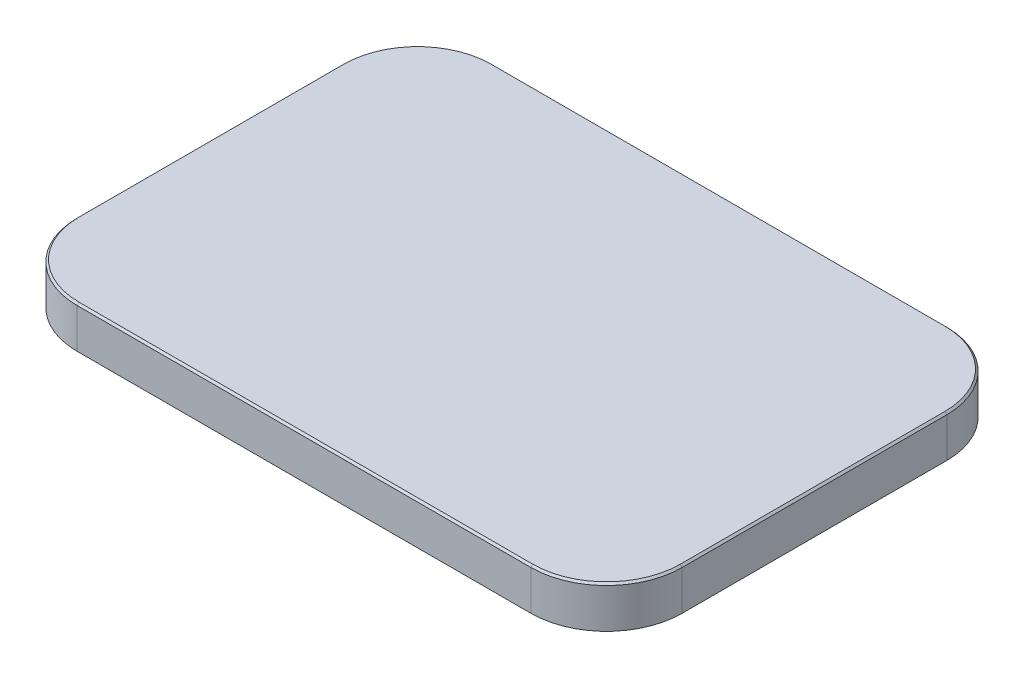
SolidWorks part; units mm, degrees
ref_plane "Front Plane" through (0, 0, 0) normal (0, 0, 1) x (1, 0, 0)
ref_plane "Top Plane" through (0, 0, 0) normal (0, 1, 0) x (1, 0, 0)
ref_plane "Right Plane" through (0, 0, 0) normal (1, 0, 0) x (0, 0, -1)
sketch "Sketch1" plane through (0, 0, 0) normal (0, 1, 0) x (1, 0, 0)
  line L1 (-80, -55) -> (80, -55)
  line L2 (-80, -55) -> (-80, 55)
  line L3 (-80, 55) -> (80, 55)
  line L4 (80, -55) -> (80, 55)
  line L5 (-80, -55) -> (80, 55) construction
  line L6 (-80, 55) -> (80, -55) construction
  point P0 (0, 0)
  dimension "D1" = 110
  dimension "D2" = 160
extrude "Boss-Extrude1" add sketch "Sketch1" against normal blind 1 contours L2 L1 L4 L3
fillet "Fillet1" radius 20 4 edges at (80, -0.5, -55) (80, -0.5, 55) (-80, -0.5, 55) (-80, -0.5, -55)
sketch "Sketch2" plane through (0, -1, 0) normal (0, -1, 0) x (1, 0, 0)
  line L0 (-79, 35) -> (-79, -35)
  line L1 (-60, -54) -> (60, -54)
  line L2 (79, -35) -> (79, 35)
  line L3 (60, 54) -> (-60, 54)
  line L4 (-60, -55) -> (60, -55)
  line L5 (80, -35) -> (80, 35)
  line L6 (60, 55) -> (-60, 55)
  line L7 (-80, 35) -> (-80, -35)
  line L8 (-60, -55) -> (60, -55)
  line L9 (80, -35) -> (80, 35)
  line L10 (60, 55) -> (-60, 55)
  line L11 (-80, 35) -> (-80, -35)
  arc A0 (-60, 54) -> (-79, 35) centre (-60, 35) ccw
  arc A1 (-79, -35) -> (-60, -54) centre (-60, -35) ccw
  arc A2 (60, -54) -> (79, -35) centre (60, -35) ccw
  arc A3 (79, 35) -> (60, 54) centre (60, 35) ccw
  arc A4 (60, -55) -> (80, -35) centre (60, -35) ccw
  arc A5 (80, 35) -> (60, 55) centre (60, 35) ccw
  arc A6 (-60, 55) -> (-80, 35) centre (-60, 35) ccw
  arc A7 (-80, -35) -> (-60, -55) centre (-60, -35) ccw
  arc A8 (60, -55) -> (80, -35) centre (60, -35) ccw
  arc A9 (80, 35) -> (60, 55) centre (60, 35) ccw
  arc A10 (-60, 55) -> (-80, 35) centre (-60, 35) ccw
  arc A11 (-80, -35) -> (-60, -55) centre (-60, -35) ccw
  dimension "D1" = 0
  dimension "D2" = 1
extrude "Boss-Extrude2" add sketch "Sketch2" along normal blind 10
fillet "Fillet2" radius 0.4 8 edges at (73.435, -1, 48.435) (79, -1, 0) (73.435, -1, -48.435) (0, -1, -54) (-73.435, -1, -48.435) (-79, -1, 0) (-73.435, -1, 48.435) (0, -1, 54)
chamfer "Chamfer1" distance 0.5 angle 45 8 edges at (0, 0, 55) (-74.1421, 0, 49.1421) (74.1421, 0, 49.1421) (-80, 0, 0) (80, 0, 0) (-74.1421, 0, -49.1421) (74.1421, 0, -49.1421) (0, 0, -55)
